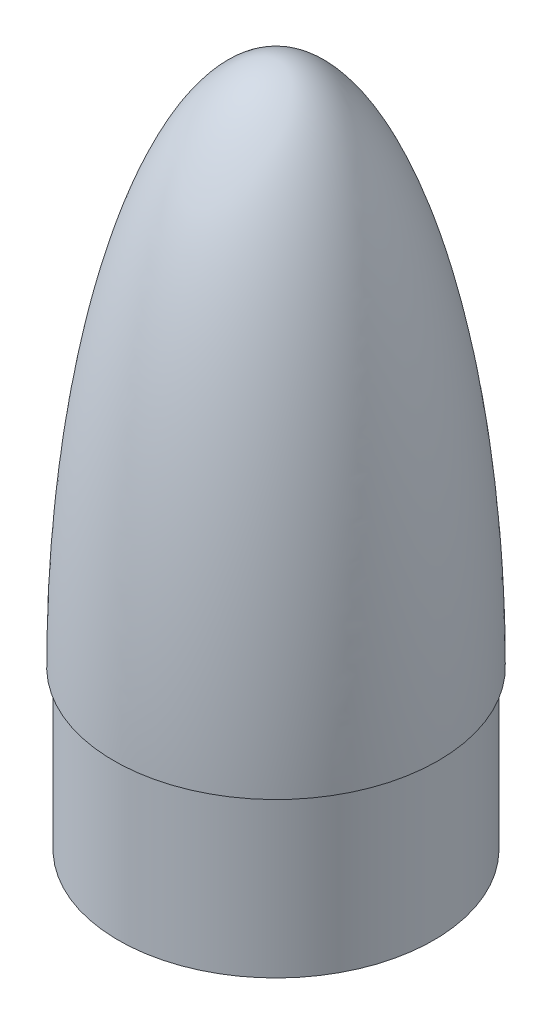
SolidWorks part; units mm, degrees
material "ABS"
ref_plane "Front Plane" through (0, 0, 0) normal (0, 0, 1) x (1, 0, 0)
ref_plane "Top Plane" through (0, 0, 0) normal (0, 1, 0) x (1, 0, 0)
ref_plane "Right Plane" through (0, 0, 0) normal (1, 0, 0) x (0, 0, -1)
sketch "Sketch1" plane through (0, 0, 0) normal (0, 0, 1) x (1, 0, 0)
  line L0 (0, 254) -> (0, 0) construction
  line L1 (78.359, 0) -> (0, 0)
  line L2 (0, 0) -> (0, 254)
  spline S0 degree 4 poles (77.9662, -25.3999) (78.0154, -23.8095) (78.1056, -20.6522) (78.1976, -16.6458) (78.2773, -11.9379) (78.3233, -7.8867) (78.3478, -4.9036) (78.3593, -1.4843) (78.3601, 0.7911) (78.3527, 3.5863) (78.3388, 5.9889) (78.318, 8.3522) (78.2903, 10.7456) (78.247, 13.7314) (78.1811, 17.3117) (78.0839, 21.4904) (77.9448, 26.2641) (77.7777, 31.0376) (77.5823, 35.8096) (77.3585, 40.5805) (77.0429, 46.5423) (76.6791, 52.5014) (76.2664, 58.4574) (75.8041, 64.4096) (75.404, 69.1689) (74.8656, 75.1148) (74.1574, 82.244) (73.2383, 90.5517) (72.0557, 100.0308) (70.7355, 109.4917) (69.2709, 118.9313) (67.25, 130.6999) (64.5017, 144.7638) (61.3086, 158.736) (57.591, 172.5772) (53.383, 186.2759) (49.2387, 198.0448) (44.4832, 209.5873) (38.9429, 220.7192) (34.2562, 228.6936) (29.8187, 235.0954) (25.6242, 240.1829) (21.9789, 243.9262) (18.5702, 246.8595) (15.4743, 249.0762) (12.5634, 250.7857) (9.7723, 252.0835) (7.0631, 253.0286) (4.2754, 253.6868) (2.188, 253.9399) (0.7672, 253.9999) (0, 254) knots 0 0 0 0 0 0.020823 0.041645 0.052056 0.062468 0.072879 0.08329 0.09112 0.098949 0.106779 0.114608 0.122438 0.130267 0.145926 0.161585 0.177244 0.192903 0.208562 0.224221 0.23988 0.271198 0.286857 0.302516 0.318175 0.333834 0.365152 0.39647 0.427788 0.459106 0.490424 0.521742 0.584379 0.647015 0.678333 0.709651 0.772287 0.810589 0.841907 0.872608 0.893486 0.912628 0.928287 0.941045 0.952387 0.962498 0.972496 0.981349 0.98995 1 1 1 1 1 construction
  spline S1 degree 4 poles (78.359, 0) (78.359, 0.5473) (78.3578, 1.6496) (78.3527, 3.5863) (78.3388, 5.9889) (78.318, 8.3522) (78.2903, 10.7456) (78.247, 13.7314) (78.1811, 17.3117) (78.0839, 21.4904) (77.9448, 26.2641) (77.7777, 31.0376) (77.5823, 35.8096) (77.3585, 40.5805) (77.0429, 46.5423) (76.6791, 52.5014) (76.2664, 58.4574) (75.8041, 64.4096) (75.404, 69.1689) (74.8656, 75.1148) (74.1574, 82.244) (73.2383, 90.5517) (72.0557, 100.0308) (70.7355, 109.4917) (69.2709, 118.9313) (67.25, 130.6999) (64.5017, 144.7638) (61.3086, 158.736) (57.591, 172.5772) (53.383, 186.2759) (49.2387, 198.0448) (44.4832, 209.5873) (38.9429, 220.7192) (34.2562, 228.6936) (29.8187, 235.0954) (25.6242, 240.1829) (21.9789, 243.9262) (18.5702, 246.8595) (15.4743, 249.0762) (12.5634, 250.7857) (9.7723, 252.0835) (7.0631, 253.0286) (4.2754, 253.6868) (2.188, 253.9399) (0.7672, 253.9999) (0, 254) knots 0.08329 0.08329 0.08329 0.08329 0.08329 0.09112 0.098949 0.106779 0.114608 0.122438 0.130267 0.145926 0.161585 0.177244 0.192903 0.208562 0.224221 0.23988 0.271198 0.286857 0.302516 0.318175 0.333834 0.365152 0.39647 0.427788 0.459106 0.490424 0.521742 0.584379 0.647015 0.678333 0.709651 0.772287 0.810589 0.841907 0.872608 0.893486 0.912628 0.928287 0.941045 0.952387 0.962498 0.972496 0.981349 0.98995 1 1 1 1 1
revolve "Revolve1" add sketch "Sketch1" angle 360 about L0
sketch "Sketch2" plane through (0, 0, 0) normal (0, -1, 0) x (1, 0, 0)
  circle A0 centre (0, 0) radius 76.2
extrude "Boss-Extrude1" add sketch "Sketch2" along normal blind 76.2
ref_axis "Axis1" through (0, 270.51, 0) along (0, -1, 0)
sketch "Sketch4" plane through (0, 0, 0) normal (0, 1, 0) x (1, 0, 0)
  line L0 (76.2, 0) -> (-78.359, 0) construction
  line L1 (0, -78.359) -> (0, 90.3851) construction
  circle A0 centre (0, 0) radius 76.2 construction
  circle A1 centre (0, 0) radius 78.359 construction
  circle A2 centre (48.26, 0) radius 17.78
  circle A3 centre (0, -48.26) radius 17.78
  circle A4 centre (-48.26, 0) radius 17.78
  circle A5 centre (0, 48.26) radius 17.78
  point P20 (0, 0)
  point P43 (0, 0.8087)
  dimension "D2" = 35.56
  dimension "D1" = 48.26
  dimension "D3" = 4
extrude "Cut-Extrude1" cut sketch "Sketch4" along normal blind 96.52
sketch "Sketch5" plane through (0, 0, 0) normal (0, 1, 0) x (1, 0, 0)
  line L0 (-83.8326, 0) -> (109.4642, 0) construction
  line L1 (0, 82.5318) -> (0, -82.1463) construction
  circle A0 centre (20.32, 0) radius 8.255
  circle A1 centre (10.16, -17.5976) radius 8.255
  circle A2 centre (-10.16, -17.5976) radius 8.255
  circle A3 centre (-20.32, 0) radius 8.255
  circle A4 centre (-10.16, 17.5976) radius 8.255
  circle A5 centre (10.16, 17.5976) radius 8.255
  point P20 (0, 0)
  dimension "D2" = 16.51
  dimension "D1" = 20.32
  dimension "D3" = 6
extrude "Cut-Extrude2" cut sketch "Sketch5" along normal blind 119.38 from offset 106.68
sketch "Sketch6" plane through (0, 0, 0) normal (0, 0, 1) x (1, 0, 0)
  line L0 (-30.48, 96.52) -> (-48.26, 117.7094)
  line L1 (-48.26, 96.52) -> (-48.26, 0) construction
  line L2 (-66.04, 96.52) -> (-30.48, 96.52) construction
  line L3 (-48.26, 117.7094) -> (-48.26, 96.52)
  line L4 (-48.26, 96.52) -> (-30.48, 96.52)
  dimension "D1" = 50
revolve "Cut-Revolve2" cut sketch "Sketch6" angle 360 about axis through (-48.26, 96.52, 0) along (0, -1, 0)
sketch "Sketch7" plane through (0, 0, 0) normal (0, 0, 1) x (1, 0, 0)
  line L0 (17.78, 96.52) -> (0, 117.7094)
  line L1 (0, 270.51) -> (0, -92.71) construction
  line L2 (-17.78, 96.52) -> (17.78, 96.52) construction
  line L3 (0, 117.7094) -> (0, 96.52)
  line L4 (0, 96.52) -> (17.78, 96.52)
  dimension "D1" = 50
ref_plane "Plane1" through (0, 0, 48.26) normal (0, 0, 1) x (1, 0, 0)
sketch "Sketch8" plane through (0, 0, 48.26) normal (0, 0, 1) x (1, 0, 0)
  line L0 (0, 96.52) -> (17.78, 96.52)
  line L1 (17.78, 96.52) -> (0, 117.7094)
  line L2 (0, 117.7094) -> (0, 96.52)
revolve "Cut-Revolve4" cut sketch "Sketch8" angle 360 about axis through (0, 96.52, 48.26) along (0, -1, 0)
sketch "Sketch9" plane through (0, 0, 0) normal (0, 0, 1) x (1, 0, 0)
  line L0 (48.26, 96.52) -> (66.04, 96.52)
  line L1 (30.48, 96.52) -> (66.04, 96.52) construction
  line L2 (66.04, 96.52) -> (48.26, 117.7094)
  line L3 (48.26, 96.52) -> (48.26, 0) construction
  line L4 (48.26, 117.7094) -> (48.26, 96.52)
  dimension "D1" = 50
revolve "Cut-Revolve5" cut sketch "Sketch9" angle 360 about axis through (48.26, 96.52, 0) along (0, -1, 0)
ref_plane "Plane2" through (0, 0, -48.26) normal (0, 0, 1) x (1, 0, 0)
sketch "Sketch11" plane through (0, 0, -48.26) normal (0, 0, 1) x (1, 0, 0)
  line L0 (0, 96.52) -> (17.78, 96.52)
  line L1 (17.78, 96.52) -> (-17.78, 96.52) construction
  line L2 (17.78, 96.52) -> (0, 117.7094)
  line L3 (0, 117.7094) -> (0, 96.52)
revolve "Cut-Revolve6" cut sketch "Sketch11" angle 360 about axis through (0, 96.52, -48.26) along (0, -1, 0)
sketch "Sketch12" plane through (0, 0, 0) normal (0, 0, 1) x (1, 0, 0)
  line L0 (-20.32, 226.06) -> (-12.065, 226.06)
  line L1 (-28.575, 226.06) -> (-12.065, 226.06) construction
  line L2 (-12.065, 226.06) -> (-20.32, 235.8979)
  line L3 (-20.32, 226.06) -> (-20.32, 106.68) construction
  line L4 (-20.32, 235.8979) -> (-20.32, 226.06)
  dimension "D1" = 50
revolve "Cut-Revolve7" cut sketch "Sketch12" angle 360 about axis through (-20.32, 226.06, 0) along (0, -1, 0)
sketch "Sketch14" plane through (0, 0, 0) normal (0, 0, 1) x (1, 0, 0)
  line L0 (20.32, 226.06) -> (28.575, 226.06)
  line L1 (12.065, 226.06) -> (28.575, 226.06) construction
  line L2 (28.575, 226.06) -> (20.32, 235.8979)
  line L3 (20.32, 226.06) -> (20.32, 106.68) construction
  line L4 (20.32, 235.8979) -> (20.32, 226.06)
  dimension "D1" = 50
revolve "Cut-Revolve8" cut sketch "Sketch14" angle 360 about L4
ref_plane "Plane3" through (0, 0, 17.5976) normal (0, 0, 1) x (1, 0, 0)
sketch "Sketch15" plane through (0, 0, 17.5976) normal (0, 0, 1) x (1, 0, 0)
  line L0 (-10.16, 226.06) -> (-1.905, 226.06)
  line L1 (-18.415, 226.06) -> (-1.905, 226.06) construction
  line L2 (-1.905, 226.06) -> (-10.16, 235.8979)
  line L3 (-10.16, 226.06) -> (-10.16, 106.68) construction
  line L4 (-10.16, 235.8979) -> (-10.16, 226.06)
  dimension "D1" = 50
revolve "Cut-Revolve9" cut sketch "Sketch15" angle 360 about axis through (-10.16, 226.06, 17.5976) along (0, -1, 0)
sketch "Sketch16" plane through (0, 0, 17.5976) normal (0, 0, 1) x (1, 0, 0)
  line L0 (10.16, 226.06) -> (18.415, 226.06)
  line L1 (1.905, 226.06) -> (18.415, 226.06) construction
  line L2 (18.415, 226.06) -> (10.16, 235.8979)
  line L3 (10.16, 226.06) -> (10.16, 106.68) construction
  line L4 (10.16, 235.8979) -> (10.16, 226.06)
  dimension "D1" = 50
revolve "Cut-Revolve10" cut sketch "Sketch16" angle 360 about L4
ref_plane "Plane4" through (0, 0, -17.5976) normal (0, 0, 1) x (1, 0, 0)
sketch "Sketch17" plane through (0, 0, -17.5976) normal (0, 0, 1) x (1, 0, 0)
  line L0 (10.16, 226.06) -> (18.415, 226.06)
  line L1 (18.415, 226.06) -> (1.905, 226.06) construction
  line L2 (18.415, 226.06) -> (10.16, 235.8979)
  line L3 (10.16, 235.8979) -> (10.16, 226.06)
revolve "Cut-Revolve11" cut sketch "Sketch17" angle 360 about L3
sketch "Sketch18" plane through (0, 0, -17.5976) normal (0, 0, 1) x (1, 0, 0)
  line L0 (-10.16, 226.06) -> (-1.905, 226.06)
  line L1 (-1.905, 226.06) -> (-18.415, 226.06) construction
  line L2 (-1.905, 226.06) -> (-10.16, 235.8979)
  line L3 (-10.16, 235.8979) -> (-10.16, 226.06)
revolve "Cut-Revolve12" cut sketch "Sketch18" angle 360 about L3
sketch "Sketch19" plane through (0, 0, 0) normal (0, 1, 0) x (1, 0, 0)
  circle A0 centre (0, 0) radius 15.24
  dimension "D1" = 30.48
extrude "Cut-Extrude3" cut sketch "Sketch19" along normal blind 101.6 from offset 25.4 offset against normal yes
sketch "Sketch20" plane through (0, 0, 0) normal (0, 0, 1) x (1, 0, 0)
  line L5 (0, 76.2) -> (15.24, 76.2)
  line L6 (-15.24, 76.2) -> (15.24, 76.2) construction
  line L7 (15.24, 76.2) -> (0, 94.3623)
  line L8 (0, 270.51) -> (0, -92.71) construction
  line L9 (0, 94.3623) -> (0, 76.2)
  dimension "D1" = 50
revolve "Cut-Revolve13" cut sketch "Sketch20" angle 360 about axis through (0, 270.51, 0) along (0, -1, 0)
sketch "Sketch21" plane through (0, -76.2, 0) normal (0, -1, 0) x (1, 0, 0)
  line L1 (-31.75, 31.75) -> (31.75, 31.75) construction
  line L2 (-31.75, 31.75) -> (-31.75, -31.75) construction
  line L3 (-31.75, -31.75) -> (31.75, -31.75) construction
  line L4 (31.75, 31.75) -> (31.75, -31.75) construction
  circle A0 centre (-44.163, 0) radius 2.54
  circle A1 centre (0, 44.163) radius 2.54
  circle A2 centre (44.163, 0) radius 2.54
  circle A3 centre (0, -44.163) radius 2.54
  point P12 (-31.75, 0)
  dimension "D1" = 63.5
  dimension "D3" = 5.08
  dimension "D5" = 12.413
  dimension "D8" = 5.08
  dimension "D9" = 5.08
  dimension "D10" = 5.08
  dimension "D2" = 63.5
  dimension "D4" = 12.413
  dimension "D6" = 12.413
  dimension "D7" = 12.413
extrude "Cut-Extrude4" cut sketch "Sketch21" against normal blind 6.35
sketch "Sketch22" plane through (0, -76.2, 0) normal (0, -1, 0) x (1, 0, 0)
  line L0 (-71.842, 0) -> (0, 71.842) construction
  line L1 (0, 71.842) -> (71.842, 0) construction
  line L2 (71.842, 0) -> (0, -71.842) construction
  line L3 (0, -71.842) -> (-71.842, 0) construction
  line L4 (0, -44.163) -> (44.163, 0) construction
  circle A0 centre (-35.921, -35.921) radius 3
  circle A1 centre (-35.921, 35.921) radius 3
  circle A2 centre (35.921, 35.921) radius 3
  circle A3 centre (35.921, -35.921) radius 3
  dimension "D6" = 6
  dimension "D7" = 6
  dimension "D8" = 6
  dimension "D9" = 6
  dimension "D1" = 101.6
  dimension "D2" = 101.6
  dimension "D3" = 50.8
  dimension "D4" = 50.8
  dimension "D5" = 90
extrude "Cut-Extrude5" cut sketch "Sketch22" against normal blind 12.7
sketch "Sketch3" plane through (0, 0, 0) normal (0, 0, 1) x (1, 0, 0)
  line L0 (0, 0) -> (50.6956, 0)
  line L1 (-76.2, 0) -> (76.2, 0) construction
  line L2 (0, 0) -> (0, 122.511)
  line L3 (0, 270.51) -> (0, -92.71) construction
  arc A0 (50.6956, 0) -> (0, 122.511) centre (-122.6821, 0) ccw
revolve "Cut-Revolve1" cut sketch "Sketch3" angle 360 about axis through (0, 270.51, 0) along (0, -1, 0)
equation "\"Bodytube_OD\"= 6.17in"
equation "\"Bodytube_ID\"= 5.998in"
equation "\"R\"= \"Bodytube_ID\" / 2"
equation "\"L\"= 30in"
